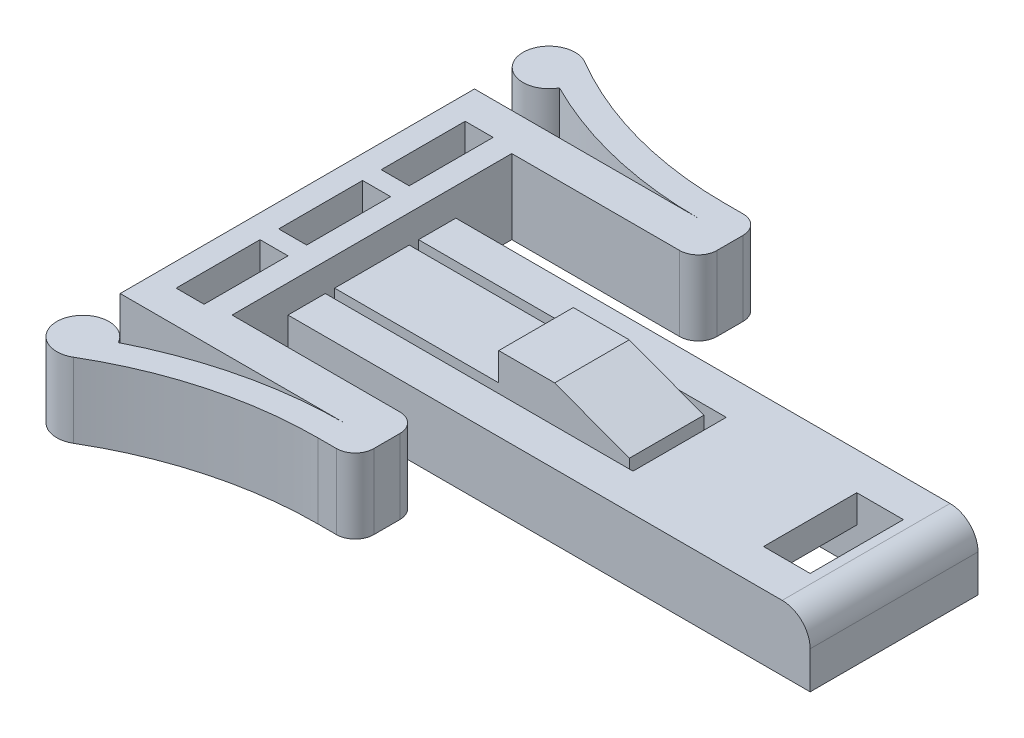
SolidWorks part; units mm, degrees
ref_plane "Спереди" through (0, 0, 0) normal (0, 0, 1) x (1, 0, 0)
ref_plane "Сверху" through (0, 0, 0) normal (0, 1, 0) x (1, 0, 0)
ref_plane "Справа" through (0, 0, 0) normal (1, 0, 0) x (0, 0, -1)
sketch "Эскиз1" plane through (0, 0, 0) normal (0, 1, 0) x (1, 0, 0)
  line L0 (-16, 0) -> (16, 0) construction
  line L1 (16, -4.5) -> (-16, -4.5)
  line L2 (16, -4.5) -> (16, 4.5)
  line L3 (16, 4.5) -> (-16, 4.5)
  line L4 (-16, -4.5) -> (-16, 4.5)
  line L5 (16, -4.5) -> (-16, 4.5) construction
  line L6 (16, 4.5) -> (-16, -4.5) construction
  line L7 (0, 4.5) -> (0, -4.5) construction
  line L8 (14, -2.5) -> (14, 2.5)
  line L9 (14, 2.5) -> (-12, 2.5)
  line L10 (14, -2.5) -> (-12, -2.5)
  line L11 (-12, 2.5) -> (-12, -2.5)
  line L12 (-16, -9.5) -> (-16, 9.5)
  line L13 (-16, -9.5) -> (-2, -9.5)
  line L14 (-12, -2.5) -> (-12, -9.5)
  line L15 (-12, -7.5) -> (-2, -7.5)
  line L16 (-2, -7.5) -> (-2, -9.5)
  line L17 (-15, -12.5) -> (-16, -12.5) construction
  line L18 (-2, -9.5) -> (-4, -9.5) construction
  line L19 (-2, -9.5) -> (-2, -10.9)
  line L20 (-4, -10.9) -> (-2, -10.9)
  line L21 (-12, 2.5) -> (-12, 9.5)
  line L22 (-12, 7.5) -> (-2, 7.5)
  line L23 (-16, 9.5) -> (-2, 9.5)
  line L24 (-2, 9.5) -> (-2, 10.9)
  line L25 (-4, 10.9) -> (-2, 10.9)
  line L26 (-2, 7.5) -> (-2, 9.5)
  line L27 (-16, -12.5) -> (-16, -9.5) construction
  arc A0 (-4, -9.5) -> (-15, -12.5) centre (-4, -31.1667) ccw
  arc A1 (-4, -10.9) -> (-14.2892, -13.7062) centre (-4, -31.1667) ccw
  circle A2 centre (-15, -12.5) radius 1.4
  arc A3 (-4, 10.9) -> (-14.2892, 13.7062) centre (-4, 31.1667) cw
  arc A4 (-4, 9.5) -> (-15, 12.5) centre (-4, 31.1667) cw
  circle A5 centre (-15, 12.5) radius 1.4
  point P0 (0, 0)
  point P13 (14, 0)
  point P18 (-16, 0)
  point P30 (-3, -10.9)
  point P36 (-3, 10.9)
  dimension "D1" = 32
  dimension "D2" = 9
  dimension "D3" = 2
  dimension "D4" = 2
  dimension "D5" = 4
  dimension "D6" = 19
  dimension "D7" = 3
  dimension "D8" = 2
  dimension "D9" = 14
  dimension "D10" = 2
  dimension "D11" = 1
  dimension "D12" = 1.4
extrude "Бобышка-Вытянуть1" add sketch "Эскиз1" along normal blind 3.5 contours L11 L21 L3 L4 L1 L14 | L21 L9 L8 L10 L14 L1 L2 L3 region at (2, 0, 4.2059) region at (-14, 0, 0)
extrude "Бобышка-Вытянуть2" add sketch "Эскиз1<3>" along normal blind 4 from offset 1 contours L14 L1 L12 L13 | L16 L15 L14 L13 | A2 A1 L20 L19 L13 A0 | A2 | L23 L12 L3 L21 | L22 L26 L23 L21 | A3 A5 A4 L23 L24 L25 | A5 | L11 L21 L3 L4 L1 L14 region at (-14, 0, 7) region at (-14, 0, 0) region at (-7, 0, 8.5) region at (-14, 0, -7) region at (-7, 0, -8.5) region at (-7.9603, 0, 10.8698) region at (-13.6819, 0, 12.1633) region at (-7.9603, 0, -10.8698) region at (-16.3115, 0, -12.1384)
sketch "Эскиз1<3>" plane through (0, 0, 0) normal (0, 1, 0) x (1, 0, 0) same geometry as "Эскиз1"
sketch "Эскиз2" plane through (0, 3.5, 0) normal (0, 1, 0) x (1, 0, 0)
  line L0 (14, 2.5) -> (-12, 2.5) construction
  line L1 (11.5, 2.5) -> (4.5, 2.5)
  line L2 (11.5, 2.5) -> (11.5, -2.5)
  line L3 (11.5, -2.5) -> (4.5, -2.5)
  line L4 (4.5, 2.5) -> (4.5, -2.5)
  line L5 (14, -2.5) -> (-12, -2.5) construction
  dimension "D1" = 2.5
  dimension "D2" = 7
extrude "Бобышка-Вытянуть3" add sketch "Эскиз2" against normal blind 1.5
fillet "Скругление1" radius 1.5 1 edges at (16, 3.5, 0) type face fillet first side face at (16, 1.75, 0) second side face at (12.75, 3.5, 0)
sketch "Эскиз3" plane through (0, 3.5, 0) normal (0, 1, 0) x (1, 0, 0)
  line L0 (-12, -2) -> (-12, 2)
  line L1 (-12, 7.5) -> (-12, -7.5) construction
  line L3 (-12, -2) -> (3.8, -2)
  line L4 (-12, -2) -> (-12, 2)
  line L5 (-12, 2) -> (3.8, 2)
  line L6 (3.8, -2) -> (3.8, 2)
  point P7 (-12, 0)
  point P8 (-12, 0)
  dimension "D1" = 4
  dimension "D2" = 0.7
extrude "Бобышка-Вытянуть4" add sketch "Эскиз3" against normal blind 1.5 contours L3 L6 L5 L0 region at (-4.1, 3.5, 0)
sketch "Эскиз4" plane through (0, 0, -2) normal (0, 0, -1) x (-1, 0, 0)
  line L0 (-3.8, 3.5) -> (0.2, 5)
  line L1 (0.2, 5) -> (3.2, 5)
  line L3 (3.2, 5) -> (3.2, 3.5)
  line L4 (12, 3.5) -> (-3.8, 3.5) construction
  line L5 (12, 5) -> (2, 5) construction
  line L10 (12, 3.5) -> (-3.8, 3.5)
  line L11 (-3.8, 3.5) -> (-3.8, 2)
  line L12 (-3.8, 2) -> (12, 2)
  line L13 (12, 2) -> (12, 3.5)
  line L14 (12, 3.5) -> (3.2, 3.5)
  line L15 (-3.8, 3.5) -> (-3.8, 2)
  line L16 (-3.8, 2) -> (12, 2)
  line L17 (12, 2) -> (12, 3.5)
  line M8 (12, 3.5) -> (-3.8, 3.5)
  dimension "D1" = 7
  dimension "D2" = 3
  dimension "D3" = 0
extrude "Бобышка-Вытянуть5" add sketch "Эскиз4" against normal blind 4 contours L3 L1 L0 M8 region at (-0.5667, 4.15, -2)
sketch "Эскиз5" plane through (0, 0, -9.5) normal (0, 0, -1) x (-1, 0, 0)
  line L0 (16, 5) -> (17.5, 2)
  line L1 (17.5, 2) -> (16, 2)
  line L2 (16, 5) -> (16, 1) construction
  line L7 (4, 1) -> (16, 1)
  line L8 (16, 1) -> (16, 5)
  line L9 (16, 5) -> (4, 5)
  line L10 (4, 5) -> (4, 1)
  line L11 (4, 1) -> (16, 1)
  line L12 (16, 1) -> (16, 2)
  line L13 (16, 5) -> (4, 5)
  line L14 (4, 5) -> (4, 1)
  line M6 (16, 1) -> (16, 5)
  dimension "D1" = 1.5
  dimension "D2" = 2
  dimension "D3" = 0
extrude "Бобышка-Вытянуть6" add sketch "Эскиз5" against normal blind 19 contours L1 L0 M6 region at (-16.5, 3, -9.5)
sketch3d "Трехмерный эскиз1"
  line L0 (-16, 2, 9.5) -> (-16, 5, 9.5)
  line L1 (-16, 5, 9.5) -> (-17.5, 2, 7.5)
  line L2 (-17.5, 2, 9.5) -> (-17.5, 2, -9.5) construction
  line L3 (-17.5, 2, 7.5) -> (-16, 2, 9.5)
  dimension "D1" = 2
extrude "Вырез-Вытянуть1" cut sketch "Трехмерный эскиз1" along direction (1, 0, 0) on the side of the normal blind 19 contours L3 L0 L1
mirror "Зеркальное отражение1" about plane through (0, 0, 0) normal (0, 0, 1) of "Вырез-Вытянуть1"
sketch "Эскиз6" plane through (0, 5, 0) normal (0, 1, 0) x (1, 0, 0)
  line L0 (-12, 7.5) -> (-12, 9.5) construction
  line L2 (-16, 9.5) -> (-4, 9.5) construction
  line L4 (-12, 9.5) -> (-16, 9.5) construction
  line L5 (-14, 9.5) -> (-14, -9.5) construction
  line L6 (-16, -9.5) -> (-4, -9.5) construction
  line L7 (-14, 2.25) -> (-14, 3.25) construction
  line L8 (-13.25, 3.25) -> (-14.75, 3.25)
  line L9 (-13.25, 3.25) -> (-13.25, 7.75)
  line L10 (-13.25, 7.75) -> (-14.75, 7.75)
  line L11 (-14.75, 3.25) -> (-14.75, 7.75)
  line L12 (-13.25, 3.25) -> (-14.75, 7.75) construction
  line L13 (-13.25, 7.75) -> (-14.75, 3.25) construction
  line L14 (-13.25, -2.25) -> (-14.75, -2.25)
  line L15 (-13.25, -2.25) -> (-13.25, 2.25)
  line L16 (-13.25, 2.25) -> (-14.75, 2.25)
  line L17 (-14.75, -2.25) -> (-14.75, 2.25)
  line L18 (-13.25, -2.25) -> (-14.75, 2.25) construction
  line L19 (-13.25, 2.25) -> (-14.75, -2.25) construction
  line L20 (-13.25, -7.75) -> (-14.75, -7.75)
  line L21 (-13.25, -7.75) -> (-13.25, -3.25)
  line L22 (-13.25, -3.25) -> (-14.75, -3.25)
  line L23 (-14.75, -7.75) -> (-14.75, -3.25)
  line L24 (-13.25, -7.75) -> (-14.75, -3.25) construction
  line L25 (-13.25, -3.25) -> (-14.75, -7.75) construction
  line L26 (-14, -3.25) -> (-14, -2.25) construction
  line L27 (-14.75, 3.25) -> (-14.75, 2.25) construction
  line L28 (-14.75, -2.25) -> (-14.75, -3.25) construction
  line L29 (-14.75, -3.25) -> (-14.756, -3.2774) construction
  point P10 (-14, 5.5)
  point P17 (-14, 0)
  point P22 (-14, -5.5)
  point P31 (-14, 0)
  dimension "D1" = 4.5
  dimension "D2" = 1
  dimension "D3" = 1.5
extrude "Вырез-Вытянуть2" cut sketch "Эскиз6" against normal up to surface (5 mm away) up to face at (1, 0, 0)
fillet "Скругление2" radius 1 1 edges at (-2, 3, -10.9) type face fillet first side face at (-3, 3, -10.9) second side face at (-2, 3, -9.2)
fillet "Скругление3" radius 1 1 edges at (-2, 3, 10.9) type face fillet first side face at (-3, 3, 10.9) second side face at (-2, 3, 9.2)
fillet "Скругление4" radius 1 1 edges at (-2, 3, 7.5) type face fillet first side face at (-7, 3, 7.5) second side face at (-2, 3, 8.7)
fillet "Скругление5" radius 1 1 edges at (-2, 3, -7.5) type face fillet first side face at (-2, 3, -8.7) second side face at (-7, 3, -7.5)
